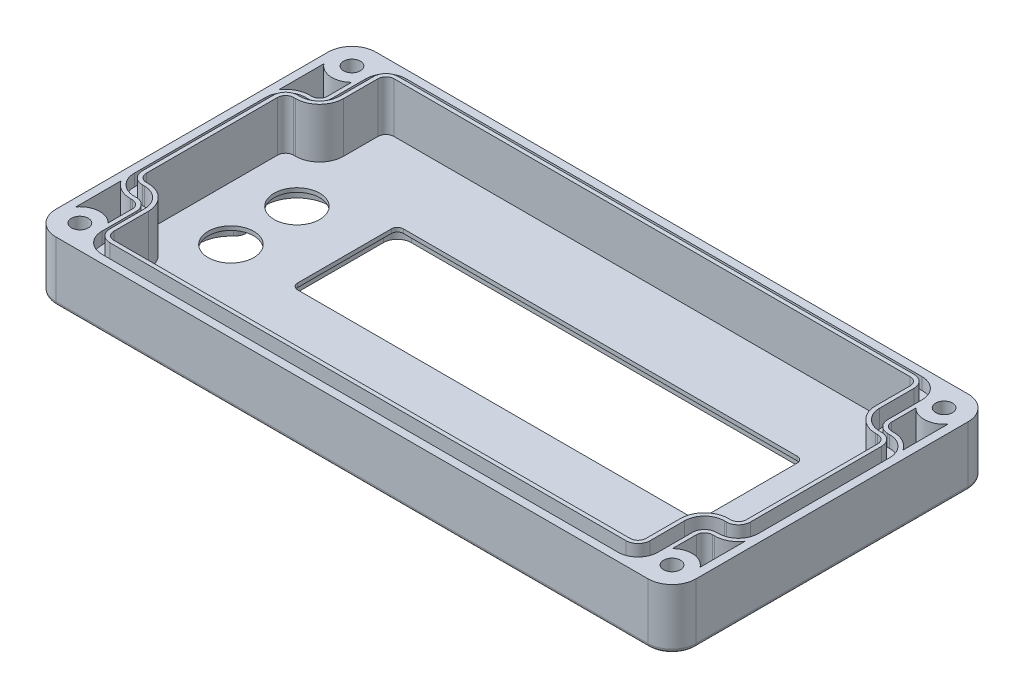
SolidWorks part; units mm, degrees
ref_plane "Спереди" through (0, 0, 0) normal (0, 0, 1) x (1, 0, 0)
ref_plane "Сверху" through (0, 0, 0) normal (0, 1, 0) x (1, 0, 0)
ref_plane "Справа" through (0, 0, 0) normal (1, 0, 0) x (0, 0, -1)
sketch "Эскиз1" plane through (0, 0, 0) normal (0, 1, 0) x (1, 0, 0)
  line L1 (-74, 40) -> (74, 40)
  line L2 (-80, 34) -> (-80, -34)
  line L3 (-74, -40) -> (74, -40)
  line L4 (80, 34) -> (80, -34)
  line L5 (-80, 40) -> (80, -40) construction
  line L6 (-80, -40) -> (80, 40) construction
  arc A0 (74, 40) -> (80, 34) centre (74, 34) cw
  arc A1 (80, -34) -> (74, -40) centre (74, -34) cw
  arc A2 (-74, -40) -> (-80, -34) centre (-74, -34) cw
  arc A3 (-80, 34) -> (-74, 40) centre (-74, 34) cw
  point P0 (0, 0)
  dimension "D3" = 6
  dimension "D1" = 160
  dimension "D2" = 80
extrude "Бобышка-Вытянуть1" add sketch "Эскиз1" along normal blind 15
sketch "Эскиз2" plane through (0, 0, 0) normal (0, 1, 0) x (1, 0, 0)
  line L0 (-66.5, 33) -> (-66.5, 24.4)
  line L1 (-72.5, 18.4) -> (-73, 18.4)
  line L2 (-75, 16.4) -> (-75, -16.4)
  line L3 (-73, -18.4) -> (-72.5, -18.4)
  line L4 (-66.5, -24.4) -> (-66.5, -33)
  line L5 (-64.5, -35) -> (64.5, -35)
  line L6 (66.5, -33) -> (66.5, -24.4)
  line L7 (72.5, -18.4) -> (73, -18.4)
  line L8 (75, -16.4) -> (75, 16.4)
  line L9 (73, 18.4) -> (72.5, 18.4)
  line L10 (66.5, 24.4) -> (66.5, 33)
  line L11 (64.5, 35) -> (-64.5, 35)
  line L12 (-75, 0) -> (75, 0) construction
  line L13 (0, 35) -> (0, -35) construction
  arc A0 (66.5, 24.4) -> (72.5, 18.4) centre (72.5, 24.4) ccw
  arc A1 (72.5, -18.4) -> (66.5, -24.4) centre (72.5, -24.4) ccw
  arc A2 (-66.5, -24.4) -> (-72.5, -18.4) centre (-72.5, -24.4) ccw
  arc A3 (-72.5, 18.4) -> (-66.5, 24.4) centre (-72.5, 24.4) ccw
  arc A4 (64.5, 35) -> (66.5, 33) centre (64.5, 33) cw
  arc A5 (73, 18.4) -> (75, 16.4) centre (73, 16.4) cw
  arc A6 (75, -16.4) -> (73, -18.4) centre (73, -16.4) cw
  arc A7 (66.5, -33) -> (64.5, -35) centre (64.5, -33) cw
  arc A8 (-64.5, -35) -> (-66.5, -33) centre (-64.5, -33) cw
  arc A9 (-73, -18.4) -> (-75, -16.4) centre (-73, -16.4) cw
  arc A10 (-75, 16.4) -> (-73, 18.4) centre (-73, 16.4) cw
  arc A11 (-66.5, 33) -> (-64.5, 35) centre (-64.5, 33) cw
  dimension "D4" = 150
  dimension "D1" = 6
  dimension "D2" = 2
  dimension "D3" = 70
  dimension "D5" = 36.8
  dimension "D6" = 133
extrude "Вырез-Вытянуть1" cut sketch "Эскиз2" along normal up to surface (15 mm away) from offset 4 up to face at (0, 15, 0)
sketch "Эскиз3" plane through (0, 0, 0) normal (0, 1, 0) x (1, 0, 0)
  line L8 (-78, 34) -> (-78, -34)
  line L9 (-74, -38) -> (74, -38)
  line L10 (78, -34) -> (78, 34)
  line L11 (74, 38) -> (-74, 38)
  line L12 (-78, 34) -> (-78, -34)
  line L13 (-74, -38) -> (74, -38)
  line L14 (78, -34) -> (78, 34)
  line L15 (74, 38) -> (-74, 38)
  line L36 (70.5, 24.4) -> (70.5, 33)
  line L37 (73, 22.4) -> (72.5, 22.4)
  line L38 (79, -16.4) -> (79, 16.4)
  line L39 (72.5, -22.4) -> (73, -22.4)
  line L40 (70.5, -33) -> (70.5, -24.4)
  line L41 (-64.5, -39) -> (64.5, -39)
  line L42 (-70.5, -24.4) -> (-70.5, -33)
  line L43 (-73, -22.4) -> (-72.5, -22.4)
  line L44 (-79, 16.4) -> (-79, -16.4)
  line L45 (-72.5, 22.4) -> (-73, 22.4)
  line L46 (-70.5, 33) -> (-70.5, 24.4)
  line L47 (64.5, 39) -> (-64.5, 39)
  line L48 (70.5, 24.4) -> (70.5, 33)
  line L49 (73, 22.4) -> (72.5, 22.4)
  line L50 (79, -16.4) -> (79, 16.4)
  line L51 (72.5, -22.4) -> (73, -22.4)
  line L52 (70.5, -33) -> (70.5, -24.4)
  line L53 (-64.5, -39) -> (64.5, -39)
  line L54 (-70.5, -24.4) -> (-70.5, -33)
  line L55 (-73, -22.4) -> (-72.5, -22.4)
  line L56 (-79, 16.4) -> (-79, -16.4)
  line L57 (-72.5, 22.4) -> (-73, 22.4)
  line L58 (-70.5, 33) -> (-70.5, 24.4)
  line L59 (64.5, 39) -> (-64.5, 39)
  circle A0 centre (-74, 34) radius 5
  arc A8 (-74, 38) -> (-78, 34) centre (-74, 34) ccw
  arc A9 (-78, -34) -> (-74, -38) centre (-74, -34) ccw
  arc A10 (74, -38) -> (78, -34) centre (74, -34) ccw
  arc A11 (78, 34) -> (74, 38) centre (74, 34) ccw
  arc A12 (-74, 38) -> (-78, 34) centre (-74, 34) ccw
  arc A13 (-78, -34) -> (-74, -38) centre (-74, -34) ccw
  arc A14 (74, -38) -> (78, -34) centre (74, -34) ccw
  arc A15 (78, 34) -> (74, 38) centre (74, 34) ccw
  arc A36 (70.5, 33) -> (64.5, 39) centre (64.5, 33) ccw
  arc A37 (70.5, 24.4) -> (72.5, 22.4) centre (72.5, 24.4) ccw
  arc A38 (79, 16.4) -> (73, 22.4) centre (73, 16.4) ccw
  arc A39 (73, -22.4) -> (79, -16.4) centre (73, -16.4) ccw
  arc A40 (72.5, -22.4) -> (70.5, -24.4) centre (72.5, -24.4) ccw
  arc A41 (64.5, -39) -> (70.5, -33) centre (64.5, -33) ccw
  arc A42 (-70.5, -33) -> (-64.5, -39) centre (-64.5, -33) ccw
  arc A43 (-70.5, -24.4) -> (-72.5, -22.4) centre (-72.5, -24.4) ccw
  arc A44 (-79, -16.4) -> (-73, -22.4) centre (-73, -16.4) ccw
  arc A45 (-73, 22.4) -> (-79, 16.4) centre (-73, 16.4) ccw
  arc A46 (-72.5, 22.4) -> (-70.5, 24.4) centre (-72.5, 24.4) ccw
  arc A47 (-64.5, 39) -> (-70.5, 33) centre (-64.5, 33) ccw
  arc A48 (70.5, 33) -> (64.5, 39) centre (64.5, 33) ccw
  arc A49 (70.5, 24.4) -> (72.5, 22.4) centre (72.5, 24.4) ccw
  arc A50 (79, 16.4) -> (73, 22.4) centre (73, 16.4) ccw
  arc A51 (73, -22.4) -> (79, -16.4) centre (73, -16.4) ccw
  arc A52 (72.5, -22.4) -> (70.5, -24.4) centre (72.5, -24.4) ccw
  arc A53 (64.5, -39) -> (70.5, -33) centre (64.5, -33) ccw
  arc A54 (-70.5, -33) -> (-64.5, -39) centre (-64.5, -33) ccw
  arc A55 (-70.5, -24.4) -> (-72.5, -22.4) centre (-72.5, -24.4) ccw
  arc A56 (-79, -16.4) -> (-73, -22.4) centre (-73, -16.4) ccw
  arc A57 (-73, 22.4) -> (-79, 16.4) centre (-73, 16.4) ccw
  arc A58 (-72.5, 22.4) -> (-70.5, 24.4) centre (-72.5, 24.4) ccw
  arc A59 (-64.5, 39) -> (-70.5, 33) centre (-64.5, 33) ccw
  dimension "D3" = 10
  dimension "D1" = 2
  dimension "D2" = 4
extrude "Вырез-Вытянуть2" cut sketch "Эскиз3" along normal up to surface (15 mm away) from offset 2.5 contours L57 A58 L58 A0 L12 A57 region at (-74.5192, 0, -25.7251) up to face at (0, 15, 0)
mirror "Зеркальное отражение1" about plane through (0, 0, 0) normal (0, 0, 1) of "Вырез-Вытянуть2"
mirror "Зеркальное отражение2" about plane through (0, 0, 0) normal (1, 0, 0) of "Зеркальное отражение1"
extrude "Вытянуть-Тонкостенный1" add sketch "Эскиз2<2>" along normal blind 1.5 from surface thin contours L11 A11 L0 A3 L1 A10 L2 A9 L3 A2 L4 A8 L5 A7 L6 A1 L7 A6 L8 A5 L9 A0 L10 A4 starting at face at (-73.7587, 15, 24.81) thin type one direction wall 1
sketch "Эскиз2<2>" plane through (0, 0, 0) normal (0, 1, 0) x (1, 0, 0) same geometry as "Эскиз2"
sketch "Эскиз6" plane through (0, 0, 0) normal (0, 1, 0) x (1, 0, 0)
  circle A0 centre (-74, 34) radius 3.75
  circle A1 centre (-74, -34) radius 3.75
  circle A2 centre (74, -34) radius 3.75
  circle A3 centre (74, 34) radius 3.75
  dimension "D1" = 7.5
extrude "Вырез-Вытянуть3" cut sketch "Эскиз6" along normal blind 3
sketch "Эскиз7" plane through (0, 0, 0) normal (0, 1, 0) x (1, 0, 0)
  circle A0 centre (-74, 34) radius 2.1
  circle A1 centre (-74, -34) radius 2.1
  circle A2 centre (74, -34) radius 2.1
  circle A3 centre (74, 34) radius 2.1
  dimension "D1" = 4.2
extrude "Вырез-Вытянуть4" cut sketch "Эскиз7" along normal up to surface (15 mm away) up to face at (0, 15, 0)
sketch "Эскиз10" plane through (0, 0, 0) normal (0, 1, 0) x (1, 0, 0)
  line L24 (67.5, 24.4) -> (67.5, 33)
  line L25 (64.5, 36) -> (-64.5, 36)
  line L26 (-67.5, 33) -> (-67.5, 24.4)
  line L27 (-72.5, 19.4) -> (-73, 19.4)
  line L28 (-76, 16.4) -> (-76, -16.4)
  line L29 (-73, -19.4) -> (-72.5, -19.4)
  line L30 (-67.5, -24.4) -> (-67.5, -33)
  line L31 (-64.5, -36) -> (64.5, -36)
  line L32 (67.5, -33) -> (67.5, -24.4)
  line L33 (72.5, -19.4) -> (73, -19.4)
  line L34 (76, -16.4) -> (76, 16.4)
  line L35 (73, 19.4) -> (72.5, 19.4)
  line L36 (67.5, 24.4) -> (67.5, 33)
  line L37 (64.5, 36) -> (-64.5, 36)
  line L38 (-67.5, 33) -> (-67.5, 24.4)
  line L39 (-72.5, 19.4) -> (-73, 19.4)
  line L40 (-76, 16.4) -> (-76, -16.4)
  line L41 (-73, -19.4) -> (-72.5, -19.4)
  line L42 (-67.5, -24.4) -> (-67.5, -33)
  line L43 (-64.5, -36) -> (64.5, -36)
  line L44 (67.5, -33) -> (67.5, -24.4)
  line L45 (72.5, -19.4) -> (73, -19.4)
  line L46 (76, -16.4) -> (76, 16.4)
  line L47 (73, 19.4) -> (72.5, 19.4)
  arc A24 (67.5, 33) -> (64.5, 36) centre (64.5, 33) ccw
  arc A25 (-64.5, 36) -> (-67.5, 33) centre (-64.5, 33) ccw
  arc A26 (-72.5, 19.4) -> (-67.5, 24.4) centre (-72.5, 24.4) ccw
  arc A27 (-73, 19.4) -> (-76, 16.4) centre (-73, 16.4) ccw
  arc A28 (-76, -16.4) -> (-73, -19.4) centre (-73, -16.4) ccw
  arc A29 (-67.5, -24.4) -> (-72.5, -19.4) centre (-72.5, -24.4) ccw
  arc A30 (-67.5, -33) -> (-64.5, -36) centre (-64.5, -33) ccw
  arc A31 (64.5, -36) -> (67.5, -33) centre (64.5, -33) ccw
  arc A32 (72.5, -19.4) -> (67.5, -24.4) centre (72.5, -24.4) ccw
  arc A33 (73, -19.4) -> (76, -16.4) centre (73, -16.4) ccw
  arc A34 (76, 16.4) -> (73, 19.4) centre (73, 16.4) ccw
  arc A35 (67.5, 24.4) -> (72.5, 19.4) centre (72.5, 24.4) ccw
  arc A36 (67.5, 33) -> (64.5, 36) centre (64.5, 33) ccw
  arc A37 (-64.5, 36) -> (-67.5, 33) centre (-64.5, 33) ccw
  arc A38 (-72.5, 19.4) -> (-67.5, 24.4) centre (-72.5, 24.4) ccw
  arc A39 (-73, 19.4) -> (-76, 16.4) centre (-73, 16.4) ccw
  arc A40 (-76, -16.4) -> (-73, -19.4) centre (-73, -16.4) ccw
  arc A41 (-67.5, -24.4) -> (-72.5, -19.4) centre (-72.5, -24.4) ccw
  arc A42 (-67.5, -33) -> (-64.5, -36) centre (-64.5, -33) ccw
  arc A43 (64.5, -36) -> (67.5, -33) centre (64.5, -33) ccw
  arc A44 (72.5, -19.4) -> (67.5, -24.4) centre (72.5, -24.4) ccw
  arc A45 (73, -19.4) -> (76, -16.4) centre (73, -16.4) ccw
  arc A46 (76, 16.4) -> (73, 19.4) centre (73, 16.4) ccw
  arc A47 (67.5, 24.4) -> (72.5, 19.4) centre (72.5, 24.4) ccw
  dimension "D1" = 1
extrude "Вырез-Вытянуть-Тонкостенный2" cut sketch "Эскиз10" against normal blind 3 from surface thin starting at face at (74, 15, 31.9) thin type one direction wall 2
fillet "Скругление1" radius 1 8 edges at (78.2426, 0, -38.2426) (80, 0, 0) (78.2426, 0, 38.2426) (0, 0, 40) (-78.2426, 0, 38.2426) (-80, 0, 0) (-78.2426, 0, -38.2426) (0, 0, -40)
sketch "Эскиз11" plane through (0, 55, 0) normal (0, -1, 0) x (-1, 0, 0)
  line L1 (44.827, 16.1787) -> (-56.5976, 16.1787)
  line L2 (44.827, 16.1787) -> (44.827, -10.2546)
  line L3 (44.827, -10.2546) -> (-56.5976, -10.2546)
  line L4 (-56.5976, 16.1787) -> (-56.5976, -10.2546)
  circle A0 centre (61.5002, 7.75) radius 5.5 construction
  circle A1 centre (61.5002, -8.75) radius 5.5 construction
  circle A2 centre (38.25, -29.2498) radius 5.5 construction
  circle A3 centre (21.75, -29.2498) radius 5.5 construction
  circle A4 centre (61.5002, 7.75) radius 5.7
  circle A5 centre (61.5002, -8.75) radius 5.7
  circle A6 centre (38.25, -29.2498) radius 5.7
  circle A7 centre (21.75, -29.2498) radius 5.7
  dimension "D1" = 0.2
extrude "Вырез-Вытянуть5" cut sketch "Эскиз11" along normal through all
fillet "Скругление2" radius 1.5 4 edges at (-44.827, 2, -16.1787) (56.5976, 2, -16.1787) (56.5976, 2, 10.2546) (-44.827, 2, 10.2546)
sketch "Эскиз12" plane through (0, 0, 0) normal (0, -1, 0) x (1, 0, 0)
  line L8 (-46.827, 8.7546) -> (-46.827, -14.6787)
  line L9 (-43.327, -18.1787) -> (55.0976, -18.1787)
  line L10 (58.5976, -14.6787) -> (58.5976, 8.7546)
  line L11 (55.0976, 12.2546) -> (-43.327, 12.2546)
  line L12 (-46.827, 8.7546) -> (-46.827, -14.6787)
  line L13 (-43.327, -18.1787) -> (55.0976, -18.1787)
  line L14 (58.5976, -14.6787) -> (58.5976, 8.7546)
  line L15 (55.0976, 12.2546) -> (-43.327, 12.2546)
  arc A8 (-43.327, 12.2546) -> (-46.827, 8.7546) centre (-43.327, 8.7546) ccw
  arc A9 (-46.827, -14.6787) -> (-43.327, -18.1787) centre (-43.327, -14.6787) ccw
  arc A10 (55.0976, -18.1787) -> (58.5976, -14.6787) centre (55.0976, -14.6787) ccw
  arc A11 (58.5976, 8.7546) -> (55.0976, 12.2546) centre (55.0976, 8.7546) ccw
  arc A12 (-43.327, 12.2546) -> (-46.827, 8.7546) centre (-43.327, 8.7546) ccw
  arc A13 (-46.827, -14.6787) -> (-43.327, -18.1787) centre (-43.327, -14.6787) ccw
  arc A14 (55.0976, -18.1787) -> (58.5976, -14.6787) centre (55.0976, -14.6787) ccw
  arc A15 (58.5976, 8.7546) -> (55.0976, 12.2546) centre (55.0976, 8.7546) ccw
  circle A43 centre (-21.75, 29.2498) radius 5.7 construction
  circle A44 centre (-38.25, 29.2498) radius 5.7 construction
  circle A45 centre (-61.5002, -7.75) radius 5.7 construction
  circle A46 centre (-61.5002, 8.75) radius 5.7 construction
  circle A59 centre (-61.5002, -7.75) radius 5.7 construction
  circle A60 centre (-61.5002, 8.75) radius 5.7 construction
  circle A61 centre (-38.25, 29.2498) radius 5.7 construction
  circle A62 centre (-21.75, 29.2498) radius 5.7 construction
  circle A63 centre (-61.5002, -7.75) radius 8.2
  circle A64 centre (-61.5002, 8.75) radius 8.2
  circle A65 centre (-38.25, 29.2498) radius 8.2
  circle A66 centre (-21.75, 29.2498) radius 8.2
  dimension "D1" = 2
  dimension "D2" = 2.5
extrude "Вырез-Вытянуть6" cut sketch "Эскиз12" against normal blind 3
sketch "Эскиз13" plane through (0, 0, 0) normal (0, -1, 0) x (1, 0, 0)
  line L1 (-66.0002, 8.75) -> (-57.0002, 8.75)
  line L2 (-66.0002, 8.75) -> (-66.0002, -7.75)
  line L3 (-66.0002, -7.75) -> (-57.0002, -7.75)
  line L4 (-57.0002, 8.75) -> (-57.0002, -7.75)
  line L5 (-38.25, 33.7498) -> (-21.75, 33.7498)
  line L6 (-38.25, 33.7498) -> (-38.25, 24.7498)
  line L7 (-38.25, 24.7498) -> (-21.75, 24.7498)
  line L8 (-21.75, 33.7498) -> (-21.75, 24.7498)
  dimension "D1" = 9
extrude "Вырез-Вытянуть8" cut sketch "Эскиз13" against normal blind 3
fillet "Скругление3" radius 3 8 edges at (-57.0002, 1.5, -0.8951) (-57.0002, 1.5, 1.895) (-66.0002, 1.5, -0.8951) (-66.0002, 1.5, 1.895) (-28.6049, 1.5, 24.7498) (-31.395, 1.5, 24.7498) (-28.6049, 1.5, 33.7498) (-31.395, 1.5, 33.7498)
